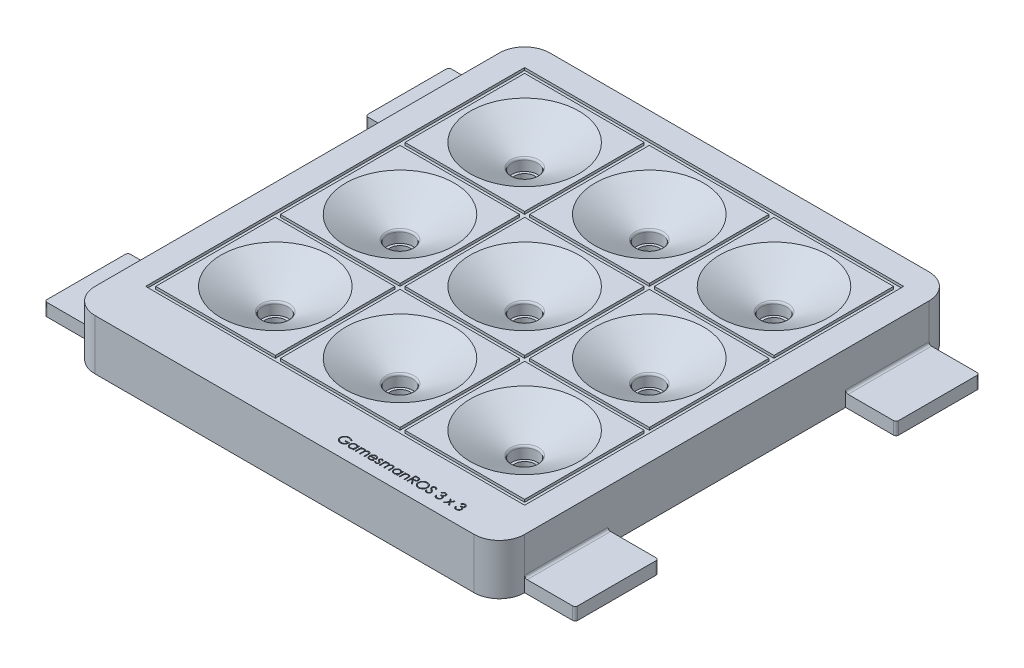
SolidWorks part; units mm, degrees
ref_plane "Front Plane" through (0, 0, 0) normal (0, 0, 1) x (1, 0, 0)
ref_plane "Top Plane" through (0, 0, 0) normal (0, 1, 0) x (1, 0, 0)
ref_plane "Right Plane" through (0, 0, 0) normal (1, 0, 0) x (0, 0, -1)
sketch "Sketch2" plane through (0, 0, 0) normal (0, 1, 0) x (1, 0, 0)
  line L1 (0, 0) -> (170, 0)
  line L2 (0, 0) -> (0, 180)
  line L3 (0, 180) -> (170, 180)
  line L4 (170, 0) -> (170, 180)
  dimension "D1" = 180
  dimension "D2" = 170
extrude "Boss-Extrude1" add sketch "Sketch2" along normal blind 20
fillet "Fillet1" radius 10 4 edges at (170, 10, -180) (0, 10, -180) (170, 10, 0) (0, 10, 0)
sketch "Sketch3" plane through (0, 20, 0) normal (0, 1, 0) x (1, 0, 0)
  line L1 (10, 170) -> (160, 170)
  line L2 (10, 170) -> (10, 20)
  line L3 (10, 20) -> (160, 20)
  line L4 (170, 10) -> (170, 170)
  line L5 (160, 180) -> (10, 180)
  line L6 (0, 170) -> (0, 10)
  line L7 (10, 0) -> (160, 0)
  line L8 (170, 10) -> (170, 170)
  line L9 (160, 180) -> (10, 180)
  line L10 (0, 170) -> (0, 10)
  line L11 (10, 0) -> (160, 0)
  line L12 (160, 170) -> (160, 20)
  line L13 (12, 168) -> (59.3333, 168)
  line L14 (12, 168) -> (12, 120.6667)
  line L15 (12, 120.6667) -> (59.3333, 120.6667)
  line L16 (59.3333, 168) -> (59.3333, 120.6667)
  line L17 (61.3333, 168) -> (108.6667, 168)
  line L18 (61.3333, 168) -> (61.3333, 120.6667)
  line L19 (61.3333, 120.6667) -> (108.6667, 120.6667)
  line L20 (108.6667, 168) -> (108.6667, 120.6667)
  line L21 (110.6667, 168) -> (158, 168)
  line L22 (110.6667, 168) -> (110.6667, 120.6667)
  line L23 (110.6667, 120.6667) -> (158, 120.6667)
  line L24 (158, 168) -> (158, 120.6667)
  line L25 (12, 118.6667) -> (59.3333, 118.6667)
  line L26 (12, 118.6667) -> (12, 71.3333)
  line L27 (12, 71.3333) -> (59.3333, 71.3333)
  line L28 (59.3333, 118.6667) -> (59.3333, 71.3333)
  line L29 (61.3333, 118.6667) -> (108.6667, 118.6667)
  line L30 (61.3333, 118.6667) -> (61.3333, 71.3333)
  line L31 (61.3333, 71.3333) -> (108.6667, 71.3333)
  line L32 (108.6667, 118.6667) -> (108.6667, 71.3333)
  line L33 (110.6667, 118.6667) -> (158, 118.6667)
  line L34 (110.6667, 118.6667) -> (110.6667, 71.3333)
  line L35 (110.6667, 71.3333) -> (158, 71.3333)
  line L36 (158, 118.6667) -> (158, 71.3333)
  line L37 (12, 69.3333) -> (59.3333, 69.3333)
  line L38 (12, 69.3333) -> (12, 22)
  line L39 (12, 22) -> (59.3333, 22)
  line L40 (59.3333, 69.3333) -> (59.3333, 22)
  line L41 (61.3333, 69.3333) -> (108.6667, 69.3333)
  line L42 (61.3333, 69.3333) -> (61.3333, 22)
  line L43 (61.3333, 22) -> (108.6667, 22)
  line L44 (108.6667, 69.3333) -> (108.6667, 22)
  line L45 (110.6667, 69.3333) -> (158, 69.3333)
  line L46 (110.6667, 69.3333) -> (110.6667, 22)
  line L47 (110.6667, 22) -> (158, 22)
  line L48 (158, 69.3333) -> (158, 22)
  arc A4 (170, 170) -> (160, 180) centre (160, 170) ccw
  arc A5 (10, 180) -> (0, 170) centre (10, 170) ccw
  arc A6 (0, 10) -> (10, 0) centre (10, 10) ccw
  arc A7 (160, 0) -> (170, 10) centre (160, 10) ccw
  arc A8 (170, 170) -> (160, 180) centre (160, 170) ccw
  arc A9 (10, 180) -> (0, 170) centre (10, 170) ccw
  arc A10 (0, 10) -> (10, 0) centre (10, 10) ccw
  arc A11 (160, 0) -> (170, 10) centre (160, 10) ccw
  dimension "D2" = 20
  dimension "D3" = 2
  dimension "D4" = 2
  dimension "D5" = 2
  dimension "D6" = 2
  dimension "D7" = 2
  dimension "D8" = 2
  dimension "D9" = 2
  dimension "D10" = 2
  dimension "D11" = 2
  dimension "D12" = 2
  dimension "D13" = 2
  dimension "D14" = 2
  dimension "D15" = 2
  dimension "D16" = 2
  dimension "D17" = 2
  dimension "D18" = 2
  dimension "D19" = 2
  dimension "D20" = 2
  dimension "D21" = 2
  dimension "D22" = 2
  dimension "D23" = 2
  dimension "D24" = 47.3333
  dimension "D25" = 2
  dimension "D26" = 2
  dimension "D27" = 2
  dimension "D28" = 47.3333
  dimension "D29" = 47.3333
  dimension "D30" = 47.3333
  dimension "D31" = 47.3333
  dimension "D32" = 47.3333
  dimension "D33" = 47.3333
  dimension "D34" = 47.3333
  dimension "D35" = 47.3333
  dimension "D36" = 47.3333
  dimension "D37" = 47.3333
  dimension "D38" = 47.3333
  dimension "D1" = 0
extrude "Cut-Extrude1" cut sketch "Sketch3" against normal blind 1 contours L12 L1 L2 L3 L13 L16 L15 L14 L17 L20 L19 L18 L21 L24 L23 L22 L25 L28 L27 L26 L29 L32 L31 L30 L33 L36 L35 L34 L37 L40 L39 L38 L41 L44 L43 L42 L45 L48 L47 L46 region at (85, 20, -169.7879)
sketch "Sketch4" plane through (0, 20, 0) normal (0, 1, 0) x (1, 0, 0)
  line L4 (170, 10) -> (170, 170)
  line L5 (160, 180) -> (10, 180)
  line L6 (0, 170) -> (0, 10)
  line L7 (10, 0) -> (160, 0)
  line L8 (170, 10) -> (170, 170)
  line L9 (160, 180) -> (10, 180)
  line L10 (0, 170) -> (0, 10)
  line L11 (10, 0) -> (160, 0)
  line L12 (59.3333, 22) -> (59.3333, 69.3333)
  line L13 (59.3333, 69.3333) -> (12, 69.3333)
  line L14 (12, 69.3333) -> (12, 22)
  line L15 (12, 22) -> (59.3333, 22)
  line L16 (59.3333, 22) -> (59.3333, 69.3333)
  line L17 (59.3333, 69.3333) -> (12, 69.3333)
  line L18 (12, 69.3333) -> (12, 22)
  line L19 (12, 22) -> (59.3333, 22)
  line L20 (59.3333, 71.3333) -> (59.3333, 118.6667)
  line L21 (59.3333, 118.6667) -> (12, 118.6667)
  line L22 (12, 118.6667) -> (12, 71.3333)
  line L23 (12, 71.3333) -> (59.3333, 71.3333)
  line L24 (59.3333, 71.3333) -> (59.3333, 118.6667)
  line L25 (59.3333, 118.6667) -> (12, 118.6667)
  line L26 (12, 118.6667) -> (12, 71.3333)
  line L27 (12, 71.3333) -> (59.3333, 71.3333)
  line L28 (108.6667, 22) -> (108.6667, 69.3333)
  line L29 (108.6667, 69.3333) -> (61.3333, 69.3333)
  line L30 (61.3333, 69.3333) -> (61.3333, 22)
  line L31 (61.3333, 22) -> (108.6667, 22)
  line L32 (108.6667, 22) -> (108.6667, 69.3333)
  line L33 (108.6667, 69.3333) -> (61.3333, 69.3333)
  line L34 (61.3333, 69.3333) -> (61.3333, 22)
  line L35 (61.3333, 22) -> (108.6667, 22)
  line L36 (158, 22) -> (158, 69.3333)
  line L37 (158, 69.3333) -> (110.6667, 69.3333)
  line L38 (110.6667, 69.3333) -> (110.6667, 22)
  line L39 (110.6667, 22) -> (158, 22)
  line L40 (158, 22) -> (158, 69.3333)
  line L41 (158, 69.3333) -> (110.6667, 69.3333)
  line L42 (110.6667, 69.3333) -> (110.6667, 22)
  line L43 (110.6667, 22) -> (158, 22)
  line L44 (158, 71.3333) -> (158, 118.6667)
  line L45 (158, 118.6667) -> (110.6667, 118.6667)
  line L46 (110.6667, 118.6667) -> (110.6667, 71.3333)
  line L47 (110.6667, 71.3333) -> (158, 71.3333)
  line L48 (158, 71.3333) -> (158, 118.6667)
  line L49 (158, 118.6667) -> (110.6667, 118.6667)
  line L50 (110.6667, 118.6667) -> (110.6667, 71.3333)
  line L51 (110.6667, 71.3333) -> (158, 71.3333)
  line L52 (108.6667, 71.3333) -> (108.6667, 118.6667)
  line L53 (108.6667, 118.6667) -> (61.3333, 118.6667)
  line L54 (61.3333, 118.6667) -> (61.3333, 71.3333)
  line L55 (61.3333, 71.3333) -> (108.6667, 71.3333)
  line L56 (108.6667, 71.3333) -> (108.6667, 118.6667)
  line L57 (108.6667, 118.6667) -> (61.3333, 118.6667)
  line L58 (61.3333, 118.6667) -> (61.3333, 71.3333)
  line L59 (61.3333, 71.3333) -> (108.6667, 71.3333)
  line L60 (59.3333, 120.6667) -> (59.3333, 168)
  line L61 (59.3333, 168) -> (12, 168)
  line L62 (12, 168) -> (12, 120.6667)
  line L63 (12, 120.6667) -> (59.3333, 120.6667)
  line L64 (59.3333, 120.6667) -> (59.3333, 168)
  line L65 (59.3333, 168) -> (12, 168)
  line L66 (12, 168) -> (12, 120.6667)
  line L67 (12, 120.6667) -> (59.3333, 120.6667)
  line L68 (108.6667, 120.6667) -> (108.6667, 168)
  line L69 (108.6667, 168) -> (61.3333, 168)
  line L70 (61.3333, 168) -> (61.3333, 120.6667)
  line L71 (61.3333, 120.6667) -> (108.6667, 120.6667)
  line L72 (108.6667, 120.6667) -> (108.6667, 168)
  line L73 (108.6667, 168) -> (61.3333, 168)
  line L74 (61.3333, 168) -> (61.3333, 120.6667)
  line L75 (61.3333, 120.6667) -> (108.6667, 120.6667)
  line L76 (158, 120.6667) -> (158, 168)
  line L77 (158, 168) -> (110.6667, 168)
  line L78 (110.6667, 168) -> (110.6667, 120.6667)
  line L79 (110.6667, 120.6667) -> (158, 120.6667)
  line L80 (158, 120.6667) -> (158, 168)
  line L81 (158, 168) -> (110.6667, 168)
  line L82 (110.6667, 168) -> (110.6667, 120.6667)
  line L83 (110.6667, 120.6667) -> (158, 120.6667)
  circle A0 centre (35.6667, 45.6667) radius 16.5
  circle A1 centre (35.6667, 95) radius 16.5
  circle A2 centre (35.6667, 144.3333) radius 16.5
  circle A3 centre (85, 144.3333) radius 16.5
  arc A4 (170, 170) -> (160, 180) centre (160, 170) ccw
  arc A5 (10, 180) -> (0, 170) centre (10, 170) ccw
  arc A6 (0, 10) -> (10, 0) centre (10, 10) ccw
  arc A7 (160, 0) -> (170, 10) centre (160, 10) ccw
  arc A8 (170, 170) -> (160, 180) centre (160, 170) ccw
  arc A9 (10, 180) -> (0, 170) centre (10, 170) ccw
  arc A10 (0, 10) -> (10, 0) centre (10, 10) ccw
  arc A11 (160, 0) -> (170, 10) centre (160, 10) ccw
  circle A12 centre (85, 95) radius 16.5
  circle A13 centre (85, 45.6667) radius 16.5
  circle A14 centre (134.3333, 45.6667) radius 16.5
  circle A15 centre (134.3333, 95) radius 16.5
  circle A16 centre (134.3333, 144.3333) radius 16.5
  dimension "D11" = 33
  dimension "D12" = 33
  dimension "D13" = 33
  dimension "D14" = 33
  dimension "D15" = 33
  dimension "D16" = 33
  dimension "D17" = 33
  dimension "D18" = 33
  dimension "D19" = 33
  dimension "D1" = 0
  dimension "D2" = 0
  dimension "D3" = 0
  dimension "D4" = 0
  dimension "D5" = 0
  dimension "D6" = 0
  dimension "D7" = 0
  dimension "D8" = 0
  dimension "D9" = 0
  dimension "D10" = 0
sketch "Sketch5" plane through (0, 20, 0) normal (0, 1, 0) x (1, 0, 0)
  circle A0 centre (35.6667, 45.6667) radius 5.05
  circle A1 centre (35.6667, 95) radius 5.05
  circle A2 centre (35.6667, 144.3333) radius 5.05
  circle A3 centre (85, 144.3333) radius 5.05
  circle A4 centre (85, 95) radius 5.05
  circle A5 centre (85, 45.6667) radius 5.05
  circle A6 centre (134.3333, 45.6667) radius 5.05
  circle A7 centre (134.3333, 95) radius 5.05
  circle A8 centre (134.3333, 144.3333) radius 5.05
  dimension "D1" = 10.1
  dimension "D2" = 10.1
  dimension "D3" = 10.1
  dimension "D4" = 10.1
  dimension "D5" = 10.1
  dimension "D6" = 10.1
  dimension "D7" = 10.1
  dimension "D8" = 10.1
  dimension "D9" = 10.1
extrude "Cut-Extrude2" cut sketch "Sketch5" against normal blind 9
chamfer "Chamfer1" distance 16.45 distance2 9 9 edges at (134.3333, 20, -139.2833) (134.3333, 20, -89.95) (134.3333, 20, -40.6167) (85, 20, -40.6167) (85, 20, -89.95) (85, 20, -139.2833) (35.6667, 20, -139.2833) (35.6667, 20, -89.95) (35.6667, 20, -40.6167) first distance on face at (134.3333, 20, -139.2833) first distance on face at (134.3333, 20, -89.95) first distance on face at (134.3333, 20, -40.6167) first distance on face at (85, 20, -40.6167) first distance on face at (85, 20, -89.95) first distance on face at (85, 20, -139.2833) first distance on face at (35.6667, 20, -139.2833) first distance on face at (35.6667, 20, -89.95) first distance on face at (35.6667, 20, -40.6167)
sketch "Sketch8" plane through (0, 11, 0) normal (0, 1, 0) x (1, 0, 0)
  circle A1 centre (35.6667, 45.6667) radius 5.05
  circle A2 centre (35.6667, 45.6667) radius 5.05
  circle A3 centre (35.6667, 95) radius 5.05
  circle A4 centre (35.6667, 95) radius 5.05
  circle A5 centre (35.6667, 144.3333) radius 5.05
  circle A6 centre (35.6667, 144.3333) radius 5.05
  circle A7 centre (85, 144.3333) radius 5.05
  circle A8 centre (85, 144.3333) radius 5.05
  circle A9 centre (85, 95) radius 5.05
  circle A10 centre (85, 95) radius 5.05
  circle A11 centre (85, 45.6667) radius 5.05
  circle A12 centre (85, 45.6667) radius 5.05
  circle A13 centre (134.3333, 45.6667) radius 5.05
  circle A14 centre (134.3333, 45.6667) radius 5.05
  circle A15 centre (134.3333, 95) radius 5.05
  circle A16 centre (134.3333, 95) radius 5.05
  circle A17 centre (134.3333, 144.3333) radius 5.05
  circle A18 centre (134.3333, 144.3333) radius 5.05
  dimension "D1" = 0
  dimension "D2" = 0
  dimension "D3" = 0
  dimension "D4" = 0
  dimension "D5" = 0
  dimension "D6" = 0
  dimension "D7" = 0
  dimension "D8" = 0
  dimension "D9" = 0
extrude "Cut-Extrude3" cut sketch "Sketch8" against normal blind 4.5
sketch "Sketch9" plane through (0, 6.5, 0) normal (0, 1, 0) x (1, 0, 0)
  circle A0 centre (35.6667, 45.6667) radius 4
  circle A1 centre (35.6667, 95) radius 4
  circle A2 centre (35.6667, 144.3333) radius 4
  circle A3 centre (85, 144.3333) radius 4
  circle A4 centre (85, 95) radius 4
  circle A5 centre (85, 45.6667) radius 4
  circle A6 centre (134.3333, 45.6667) radius 4
  circle A7 centre (134.3333, 95) radius 4
  circle A8 centre (134.3333, 144.3333) radius 4
  dimension "D1" = 8
  dimension "D2" = 8
  dimension "D3" = 8
  dimension "D4" = 8
  dimension "D5" = 8
  dimension "D6" = 8
  dimension "D7" = 8
  dimension "D8" = 8
  dimension "D9" = 8
extrude "Cut-Extrude4" cut sketch "Sketch9" against normal blind 6.5
fillet "Fillet2" radius 1 9 edges at (134.3333, 11, -139.2833) (134.3333, 11, -89.95) (134.3333, 11, -40.6167) (85, 11, -40.6167) (85, 11, -89.95) (85, 11, -139.2833) (35.6667, 11, -139.2833) (35.6667, 11, -89.95) (35.6667, 11, -40.6167)
sketch "Sketch10" plane through (0, 0, 0) normal (0, -1, 0) x (1, 0, 0)
  line L1 (0, -10) -> (-20, -10)
  line L2 (0, -10) -> (0, -43)
  line L3 (0, -43) -> (-20, -43)
  line L4 (10, -180) -> (160, -180)
  line L5 (170, -170) -> (170, -10)
  line L6 (160, 0) -> (10, 0)
  line L7 (0, -10) -> (0, -170)
  line L8 (10, -180) -> (160, -180)
  line L9 (170, -170) -> (170, -10)
  line L10 (160, 0) -> (10, 0)
  line L11 (0, -10) -> (0, -170)
  line L12 (-20, -10) -> (-20, -43)
  line L13 (0, -170) -> (-20, -170)
  line L14 (0, -170) -> (0, -137)
  line L15 (0, -137) -> (-20, -137)
  line L16 (-20, -170) -> (-20, -137)
  line L17 (170, -137) -> (190, -137)
  line L18 (170, -137) -> (170, -170)
  line L19 (170, -170) -> (190, -170)
  line L20 (190, -137) -> (190, -170)
  line L21 (170, -10) -> (190, -10)
  line L22 (170, -10) -> (170, -43)
  line L23 (170, -43) -> (190, -43)
  line L24 (190, -10) -> (190, -43)
  arc A4 (160, -180) -> (170, -170) centre (160, -170) ccw
  arc A5 (170, -10) -> (160, 0) centre (160, -10) ccw
  arc A6 (10, 0) -> (0, -10) centre (10, -10) ccw
  arc A7 (0, -170) -> (10, -180) centre (10, -170) ccw
  arc A8 (160, -180) -> (170, -170) centre (160, -170) ccw
  arc A9 (170, -10) -> (160, 0) centre (160, -10) ccw
  arc A10 (10, 0) -> (0, -10) centre (10, -10) ccw
  arc A11 (0, -170) -> (10, -180) centre (10, -170) ccw
  line M29 (170, -170) -> (170, -10)
  line M33 (0, -10) -> (0, -170)
  dimension "D2" = 20
  dimension "D3" = 20
  dimension "D4" = 20
  dimension "D5" = 20
  dimension "D6" = 33
  dimension "D7" = 33
  dimension "D8" = 33
  dimension "D9" = 33
  dimension "D1" = 0
extrude "Boss-Extrude2" add sketch "Sketch10" against normal blind 5 contours L1 L12 L3 M33 | L16 L13 L11 L15 | L20 L17 L19 M29 | L24 L21 L23 M29 region at (-10, 0, -26.5) region at (-10, 0, -153.5) region at (180, 0, -26.5) region at (180, 0, -153.5)
fillet "Fillet3" radius 1 4 edges at (170, 5, -153.5) (170, 5, -26.5) (0, 5, -26.5) (0, 5, -153.5)
fillet "Fillet4" radius 1 8 edges at (190, 2.5, -43) (190, 2.5, -10) (190, 2.5, -137) (190, 2.5, -170) (-20, 2.5, -170) (-20, 2.5, -137) (-20, 2.5, -43) (-20, 2.5, -10)
sketch "Sketch12" plane through (0, 20, 0) normal (0, 1, 0) x (1, 0, 0)
  text T0 "GamesmanROS 3 x 3"
extrude "Cut-Extrude5" cut sketch "Sketch12" against normal blind 1
